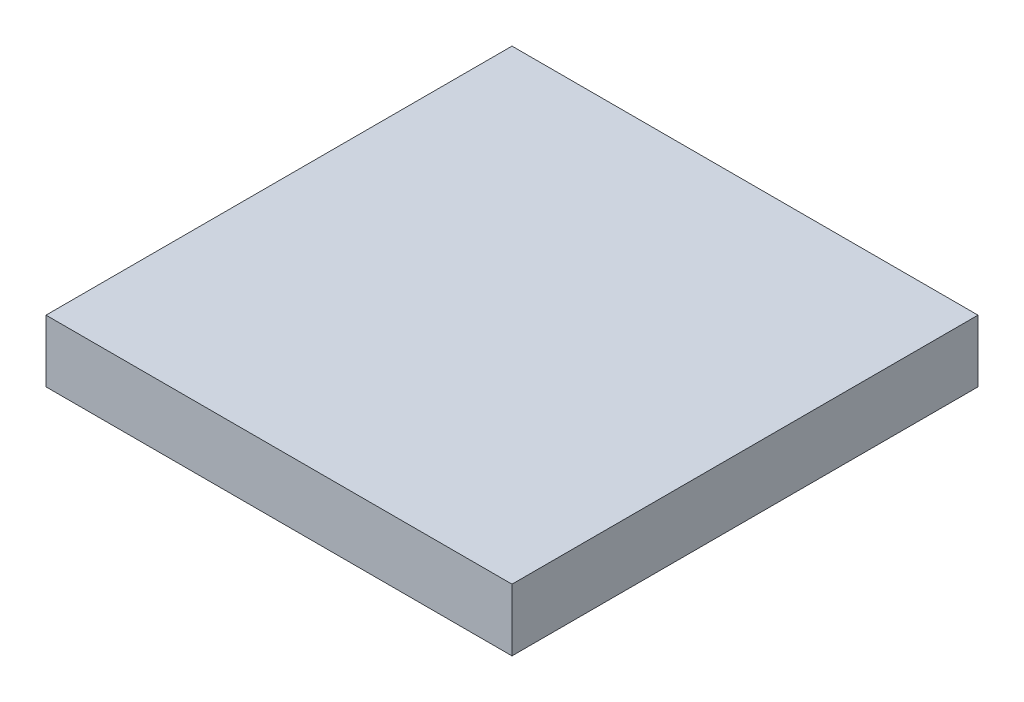
SolidWorks part; units mm, degrees
ref_plane "Front Plane" through (0, 0, 0) normal (0, 0, 1) x (1, 0, 0)
ref_plane "Top Plane" through (0, 0, 0) normal (0, 1, 0) x (1, 0, 0)
ref_plane "Right Plane" through (0, 0, 0) normal (1, 0, 0) x (0, 0, -1)
sketch "Sketch2" plane through (0, 0, 0) normal (0, 1, 0) x (1, 0, 0)
  circle A0 centre (0, 0) radius 76.2
  circle A1 centre (0, 0) radius 69.85
  arc A2 (0, 69.85) -> (0, 0) centre (0, 34.925) cw
  arc A3 (0, 0) -> (0, -69.85) centre (0, -34.925) ccw
  circle A4 centre (0, 34.925) radius 10.16
  circle A5 centre (0, -34.925) radius 10.16
  dimension "D1" = 152.4
  dimension "D2" = 139.7
  dimension "D3" = 20.32
sketch "Sketch3" plane through (0, 0, 0) normal (0, 1, 0) x (1, 0, 0)
  circle A0 centre (0, 0) radius 76.2 construction
  circle A1 centre (0, 0) radius 76.2
extrude "Boss-Extrude1" add sketch "Sketch3" along normal blind 12.7
sketch "Sketch6" plane through (0, 12.7, 0) normal (0, 1, 0) x (1, 0, 0)
  circle A0 centre (0, 0) radius 69.85 construction
  circle A1 centre (0, 0) radius 69.85
extrude "Cut-Extrude3" cut sketch "Sketch6" against normal blind 2.54
sketch "Sketch8" plane through (0, 10.16, 0) normal (0, 1, 0) x (1, 0, 0)
  circle A0 centre (0, 34.925) radius 10.16 construction
  circle A1 centre (0, 0) radius 69.85 construction
  arc A2 (0, 0) -> (0, -69.85) centre (0, -34.925) ccw construction
  arc A3 (0, 0) -> (0, 69.85) centre (0, 34.925) ccw construction
  circle A4 centre (0, 34.925) radius 10.16
  circle A5 centre (0, 0) radius 69.85
  arc A6 (0, 0) -> (0, -69.85) centre (0, -34.925) ccw
  arc A7 (0, 0) -> (0, 69.85) centre (0, 34.925) ccw
extrude "Boss-Extrude4" add sketch "Sketch8" along normal blind 2.54 contours A6 A7 A5 A4 region at (-23.2163, 10.16, -16.6909)
sketch "Sketch9" plane through (0, 10.16, 0) normal (0, 1, 0) x (1, 0, 0)
  circle A0 centre (0, -34.925) radius 10.16 construction
  circle A1 centre (0, -34.925) radius 10.16
extrude "Boss-Extrude5" add sketch "Sketch9" along normal blind 2.54
ref_plane "Plane1" through (0, 6.35, 0) normal (0, 1, 0) x (1, 0, 0)
mirror "Mirror1" about plane through (0, 6.35, 0) normal (0, 1, 0) of "Cut-Extrude3", "Boss-Extrude4", "Boss-Extrude5"
sketch "Sketch10" plane through (0, 12.7, 0) normal (0, 1, 0) x (1, 0, 0)
  line L0 (0, 0) -> (0, 76.2) construction
  line L1 (0, 76.2) -> (0, 82.55) construction
  line L2 (0, 82.55) -> (0, 120.65) construction
  line L3 (0, 120.65) -> (0, 158.75) construction
  line L4 (0, 82.55) -> (31.75, 120.65)
  line L5 (31.75, 120.65) -> (0, 158.75)
  line L6 (0, 158.75) -> (-31.75, 120.65)
  line L7 (-31.75, 120.65) -> (0, 82.55)
  line L8 (-31.75, 120.65) -> (0, 120.65) construction
  line L9 (0, 120.65) -> (31.75, 120.65) construction
  circle A0 centre (0, 0) radius 76.2 construction
  dimension "D1" = 0
  dimension "D2" = 38.1
  dimension "D3" = 63.5
  dimension "D4" = 6.35
extrude "Boss-Extrude6" add sketch "Sketch10" against normal up to surface (12.7 mm away) separate body contours L7 L4 L5 L6 up to face at (23.2833, 0, 0)
sketch "Sketch11" plane through (0, 6.35, 0) normal (0, 1, 0) x (1, 0, 0)
  line L0 (0, 158.75) -> (-31.75, 120.65) construction
  line L1 (-31.75, 120.65) -> (0, 82.55) construction
  line L2 (0, 82.55) -> (31.75, 120.65) construction
  line L3 (31.75, 120.65) -> (0, 158.75) construction
  line L4 (0, 158.75) -> (-31.75, 120.65)
  line L5 (-31.75, 120.65) -> (0, 82.55)
  line L6 (0, 82.55) -> (31.75, 120.65)
  line L7 (31.75, 120.65) -> (0, 158.75)
  line L8 (0, 82.55) -> (0, 76.2) construction
  line L10 (-5.08, 70.104) -> (5.08, 70.104)
  line L11 (-5.08, 70.104) -> (-5.08, 88.646)
  line L12 (-5.08, 88.646) -> (5.08, 88.646)
  line L13 (5.08, 70.104) -> (5.08, 88.646)
  line L14 (-5.08, 70.104) -> (5.08, 88.646) construction
  line L15 (-5.08, 88.646) -> (5.08, 70.104) construction
  circle A0 centre (0, 0) radius 76.2 construction
  circle A1 centre (0, 0) radius 76.2
  point P7 (0, 79.375)
  dimension "D1" = 10.16
extrude "Boss-Extrude7" add sketch "Sketch11" along normal blind 3.81 and the other way blind 3.81 separate body contours A1 L13 L6 L5 L11 region at (0, 6.35, -81.0344)
sketch "Sketch12" plane through (0, 12.7, 0) normal (0, 1, 0) x (1, 0, 0)
  line L0 (0, 158.75) -> (0, 82.55) construction
  circle A0 centre (0, 120.65) radius 19.05
  point P6 (0, 0)
  point P7 (0, 88.0745)
  point P8 (0, 0)
  dimension "D1" = 38.1
extrude "Cut-Extrude4" cut sketch "Sketch12" against normal blind 2.54
mirror "Mirror2" about plane through (0, 6.35, 0) normal (0, 1, 0) of "Cut-Extrude4"
pattern_circular "CirPattern3" count 4 over 360 about axis through (0, 12.7, 0) along (0, -1, 0) of "Boss-Extrude7"
combine bodies "Combine2" operation type add bodies to combine 113 111 118 121 117 120 116 119 109
sketch "Sketch13" plane through (0, 10.16, 0) normal (0, 1, 0) x (1, 0, 0)
  line L0 (-14.9802, 132.4184) -> (14.9802, 132.4184) construction
  line L1 (0, 120.65) -> (0, 132.4184) construction
  circle A3 centre (0, 120.65) radius 19.05
  circle A4 centre (0, 120.65) radius 19.05 construction
  text T0 "<r270> 北</r>\r\n" font "@Microsoft YaHei UI" height in points 70
  dimension "D1" = 0
extrude "Boss-Extrude8" add sketch "Sketch13" along normal blind 2.54
sketch "Sketch14" plane through (0, 0, 0) normal (0, 0, 1) x (1, 0, 0)
  line L0 (0, 0) -> (0, 12.7) construction
  line L1 (0, 12.7) -> (17.78, 12.7)
  line L2 (17.78, 12.7) -> (17.78, 17.78)
  line L3 (17.78, 17.78) -> (15.24, 17.78)
  line L4 (0, 12.7) -> (0, 15.24)
  line L5 (0, 15.24) -> (-3.5426, 15.24) construction
  arc A0 (15.24, 17.78) -> (0, 15.24) centre (0, 62.23) cw
  dimension "D3" = 17.78
  dimension "D1" = 12.7
  dimension "D2" = 3.5426
  dimension "D4" = 5.08
  dimension "D5" = 2.54
  dimension "D6" = 2.54
revolve "Revolve1" add sketch "Sketch14" angle 360 about L4
mirror "Mirror3" about plane through (0, 6.35, 0) normal (0, 1, 0) of "Revolve1"
mirror "Mirror4" about plane through (0, 6.35, 0) normal (0, 1, 0) of "Boss-Extrude8"
sketch "Sketch15" plane through (0, 12.7, 0) normal (0, 1, 0) x (1, 0, 0)
  line L0 (0, 15.24) -> (0, -15.24) construction
  circle A0 centre (0, 0) radius 15.24 construction
  circle A1 centre (0, 0) radius 5.715
  dimension "D1" = 11.43
extrude "Boss-Extrude9" add sketch "Sketch15" against normal blind 12.7
sketch "Sketch16" plane through (0, 0, 0) normal (0, 1, 0) x (1, 0, 0)
  line L1 (190.5, -190.5) -> (-190.5, -190.5)
  line L2 (190.5, -190.5) -> (190.5, 190.5)
  line L3 (190.5, 190.5) -> (-190.5, 190.5)
  line L4 (-190.5, -190.5) -> (-190.5, 190.5)
  line L5 (190.5, -190.5) -> (-190.5, 190.5) construction
  line L6 (190.5, 190.5) -> (-190.5, -190.5) construction
  point P0 (0, 0)
  dimension "D1" = 381
  dimension "D2" = 381
extrude "Boss-Extrude10" add sketch "Sketch16" along normal blind 50.8 separate body
